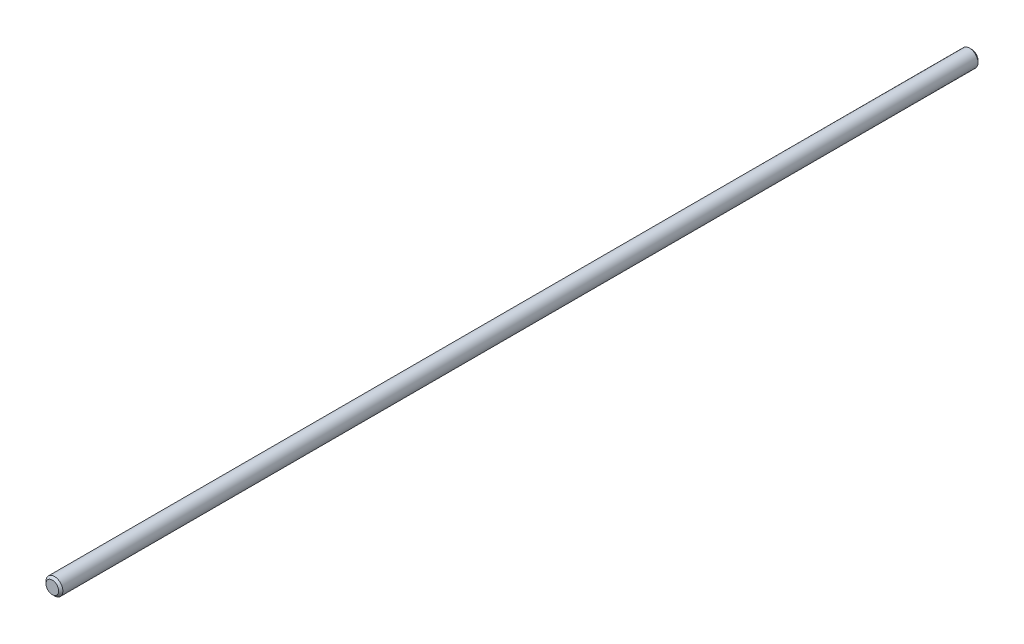
SolidWorks part; units mm, degrees
ref_plane "Piano frontale" through (0, 0, 0) normal (0, 0, 1) x (1, 0, 0)
ref_plane "Piano superiore" through (0, 0, 0) normal (0, 1, 0) x (1, 0, 0)
ref_plane "Piano destro" through (0, 0, 0) normal (1, 0, 0) x (0, 0, -1)
sketch "Schizzo1" plane through (0, 0, 0) normal (0, 0, 1) x (1, 0, 0)
  circle A0 centre (0, 0) radius 4
  dimension "D1" = 8
extrude "Estrusione-Estrusione1" add sketch "Schizzo1" along normal blind 436
chamfer "Smusso1" distance 1 angle 45 2 edges at (4, 0, 436) (4, 0, 0)
sketch "Schizzo2" plane through (0, 0, 0) normal (0, 1, 0) x (1, 0, 0)
  line L0 (4, -435) -> (4, -1) construction
  line L1 (4, -435) -> (4, -1) construction
  line L2 (4, -435) -> (-4, -435) construction
  line L3 (4, -1) -> (-4, -1) construction
